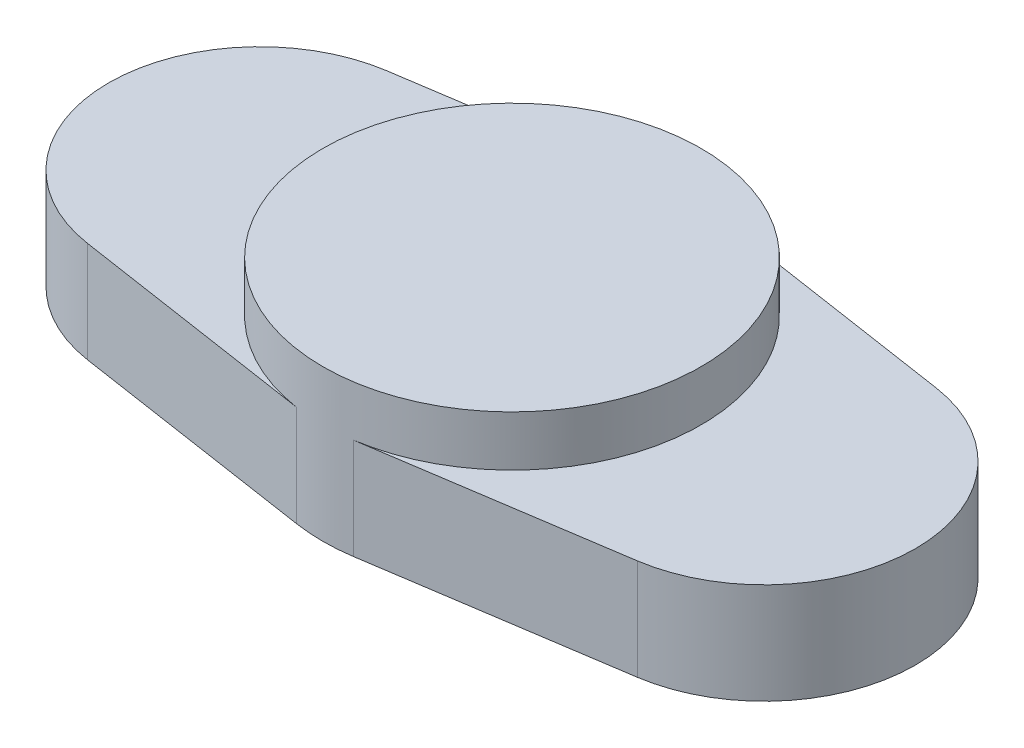
SolidWorks part; units mm, degrees
ref_plane "Front Plane" through (0, 0, 0) normal (0, 0, 1) x (1, 0, 0)
ref_plane "Top Plane" through (0, 0, 0) normal (0, 1, 0) x (1, 0, 0)
ref_plane "Right Plane" through (0, 0, 0) normal (1, 0, 0) x (0, 0, -1)
sketch "Sketch1" plane through (0, 0, 0) normal (0, 1, 0) x (1, 0, 0)
  line L0 (0, 0) -> (5, 0) construction
  line L1 (0.5625, 3.7076) -> (5.45, 2.9661)
  line L2 (0.5625, -3.7076) -> (5.45, -2.9661)
  line L3 (0, 0) -> (-5, 0) construction
  line L4 (-5.45, 2.9661) -> (-0.5625, 3.7076)
  line L5 (-5.45, -2.9661) -> (-0.5625, -3.7076)
  arc A0 (0.5625, 3.7076) -> (-0.5625, 3.7076) centre (0, 0) ccw
  arc A1 (5.45, -2.9661) -> (5.45, 2.9661) centre (5, 0) ccw
  arc A2 (-5.45, 2.9661) -> (-5.45, -2.9661) centre (-5, 0) ccw
  arc A3 (-0.5625, -3.7076) -> (0.5625, -3.7076) centre (0, 0) ccw
  dimension "D1" = 7.5
  dimension "D2" = 6
  dimension "D4" = 5
  dimension "D5" = 6
  dimension "D3" = 5
extrude "Boss-Extrude1" add sketch "Sketch1" along normal blind 2
sketch "Sketch2" plane through (0, 2, 0) normal (0, 1, 0) x (1, 0, 0)
  circle A0 centre (0, 0) radius 3.75
extrude "Boss-Extrude2" add sketch "Sketch2" along normal blind 1
sketch "Sketch3" plane through (0, 0, 0) normal (0, -1, 0) x (1, 0, 0)
  circle A0 centre (0, 0) radius 2.75
  dimension "D1" = 5.5
extrude "Cut-Extrude1" cut sketch "Sketch3" against normal blind 1
